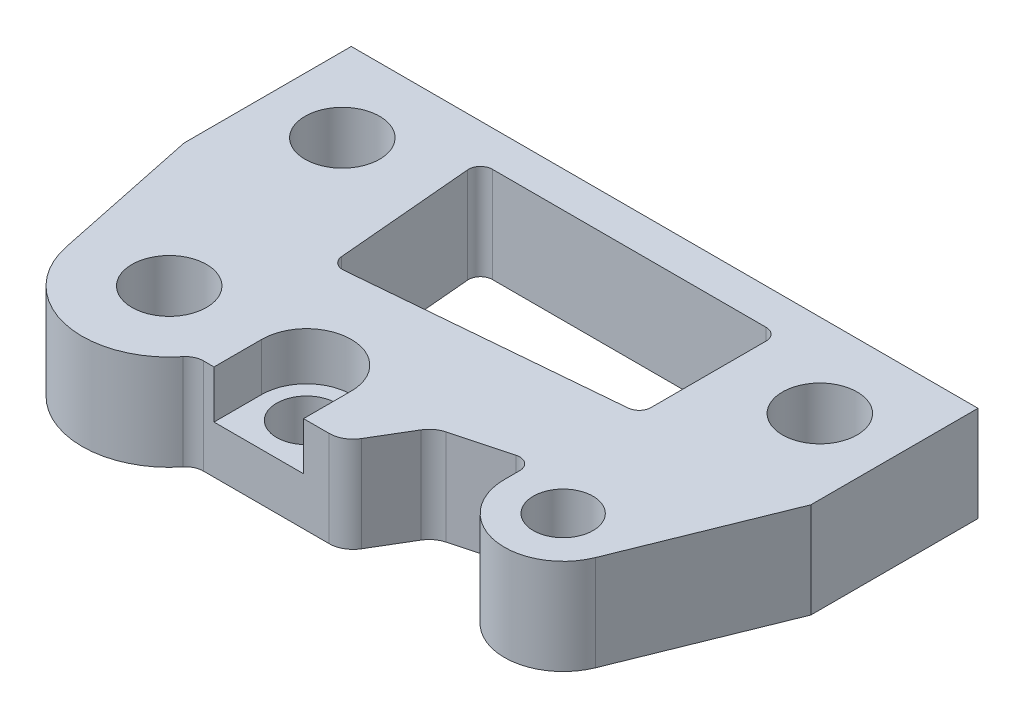
SolidWorks part; units mm, degrees
note: '?' marks a value the reader was unsure of.
material "7075-T6 (SN)"
ref_plane "X-Y Datum" through (0, 0, 0) normal (0, 0, 1) x (1, 0, 0)
ref_plane "X-Z Datum" through (0, 0, 0) normal (0, 1, 0) x (1, 0, 0)
ref_plane "Y-Z Datum" through (0, 0, 0) normal (1, 0, 0) x (0, 0, -1)
other "Graphic1"
other "Graphic (Closed) -1"
other "Graphic2"
other "Graphic (Closed) -2"
sketch "Sketch1" plane through (0, 0, 0) normal (0, 1, 0) x (1, 0, 0)
  line L0 (38.1, -5.08) -> (6.099, -5.08)
  line L1 (54.2925, 13.97) -> (-12.3825, 13.97) construction
  line L4 (54.2925, 31.75) -> (-12.3825, 31.75)
  line L6 (46.355, 22.86) -> (-4.445, 22.86) construction
  line L7 (54.2925, 31.75) -> (54.2925, 13.97)
  line L8 (-12.3825, 31.75) -> (-12.3825, 13.97)
  line L19 (48.26, 0) -> (54.2925, 13.97)
  line L21 (-7.9375, 0) -> (-12.3825, 13.97)
  line L28 (17.1395, -0.1867) -> (14.8786, 3.0422)
  line L30 (16.5708, 1.8211) -> (13.97, 0) construction
  line L31 (16.009, 1.4277) -> (11.1341, 1.4277) construction
  circle A0 centre (0, 0) radius 3.9688
  circle A1 centre (41.91, 0) radius 3.175
  circle A2 centre (46.355, 22.86) radius 3.9688
  circle A3 centre (-4.445, 22.86) radius 3.9687
  arc A4 (48.26, 0) -> (38.1, -5.08) centre (41.91, 0) cw
  arc A5 (6.099, -5.08) -> (-7.9375, 0) centre (0, 0) cw
  arc A12 (17.1395, -0.1867) -> (14.8786, 3.0422) centre (13.97, 0) cw
  point P22 (16.009, 1.4277)
  dimension "D2" = 6.35
  dimension "D7" = 7.9375
  dimension "D8" = 6.35
  dimension "D12" = 0.6858
  dimension "D10" = 7.9375
  dimension "D17" = 35
  dimension "D19" = 7.9375
  dimension "D18" = 19.05
  dimension "D14" = 3.9418
  dimension "D20" = 7.9375
  dimension "D3" = 50.8
  dimension "D4" = 17.78
  dimension "D5" = 8.89
  dimension "D6" = 31.75
  dimension "D9" = 41.91
  dimension "D11" = 7.9375
  dimension "D13" = 3.175
  dimension "D15" = 13.97
  dimension "D16" = 5.08
  dimension "D21" = 4.445
  dimension "D22" = 66.644
  dimension "D23" = 72.35
extrude "Boss-Extrude1" [suppressed] add sketch "Sketch1" against normal blind 10.16
sketch "Sketch2" [suppressed] plane through (0, 0, 0) normal (0, -1, 0) x (1, 0, 0)
  line L0 (9.2075, 0) -> (9.2075, 5.08)
  line L1 (6.099, 5.08) -> (38.1, 5.08) construction
  line L2 (9.2075, 5.08) -> (18.7325, 5.08)
  line L3 (18.7325, 5.08) -> (18.7325, 0)
  arc A0 (9.2075, 0) -> (18.7325, 0) centre (13.97, 0) ccw
  dimension "D1" = 9.525
extrude "Cut-Extrude1" [suppressed] cut sketch "Sketch2" along normal blind 5.08
ref_point "Point1" [suppressed]
ref_point "Point2" [suppressed]
ref_axis "Axis4" [suppressed] through (0, -10.16, 0) along (0, 1, 0)?
sketch "Sketch3" plane through (0, 0, 0) normal (0, 1, 0) x (1, 0, 0)
  line L0 (14.605, 0) -> (11.43, 0) construction
  line L1 (17.7745, -0.1867) -> (15.5136, 3.0422)
  line L2 (16.644, 1.4277) -> (14.605, 0) construction
  line L3 (54.2925, 31.75) -> (-12.3825, 31.75)
  line L4 (-12.3825, 31.75) -> (-12.3825, 13.97)
  line L5 (-12.3825, 13.97) -> (54.2925, 13.97) construction
  line L6 (54.2925, 13.97) -> (54.2925, 31.75)
  line L7 (54.2925, 13.97) -> (47.7027, -2.3404)
  line L10 (54.2925, 22.86) -> (46.355, 22.86) construction
  line L11 (46.355, 22.86) -> (-4.445, 22.86) construction
  line L12 (-4.445, 22.86) -> (-12.3825, 22.86) construction
  line L13 (8.7243, -5.08) -> (22.098, -5.08)
  line L16 (34.0652, 2.8527) -> (28.1745, 1.2818)
  line L17 (26.6476, 0.1288) -> (24.2794, -3.8412)
  line L18 (36.83, 14.4292) -> (36.83, 26.67)
  line L19 (35.56, 27.94) -> (6.4423, 27.94)
  line L20 (5.1772, 26.5593) -> (6.4612, 11.8834)
  line L21 (7.837, 10.7289) -> (35.6707, 13.164)
  line L22 (35.6624, 0) -> (35.6624, 1.6256)
  line L24 (-9.0759, -1.892) -> (-12.3825, 13.97)
  circle A0 centre (0, 0) radius 3.9687
  circle A1 centre (-4.445, 22.86) radius 3.9688
  circle A2 centre (46.355, 22.86) radius 3.9687
  circle A3 centre (41.91, 0) radius 3.175
  arc A4 (15.5136, 3.0422) -> (17.7745, -0.1867) centre (14.605, 0) ccw
  arc A5 (47.7027, -2.3404) -> (35.6624, 0) centre (41.91, 0) cw
  arc A6 (7.2372, -5.7944) -> (-9.0759, -1.892) centre (0, 0) cw
  arc A7 (22.098, -5.08) -> (24.2794, -3.8412) centre (22.098, -2.54) ccw
  arc A8 (26.6476, 0.1288) -> (28.1745, 1.2818) centre (28.829, -1.1724) cw
  arc A10 (6.4612, 11.8834) -> (7.837, 10.7289) centre (7.7263, 11.9941) ccw
  arc A11 (5.1772, 26.5593) -> (6.4423, 27.94) centre (6.4423, 26.67) cw
  arc A12 (35.56, 27.94) -> (36.83, 26.67) centre (35.56, 26.67) cw
  arc A13 (35.6707, 13.164) -> (36.83, 14.4292) centre (35.56, 14.4292) ccw
  arc A14 (34.0652, 2.8527) -> (35.6624, 1.6256) centre (34.3924, 1.6256) cw
  arc A16 (7.2372, -5.7944) -> (8.7243, -5.08) centre (8.7243, -6.985) cw
  point P14 (54.2925, 22.86)
  point P44 (6.5718, 10.6182)
  point P47 (5.0564, 27.94)
  point P52 (36.83, 13.2655)
  dimension "D1" = 7.9375
  dimension "D2" = 7.9375
  dimension "D3" = 6.35
  dimension "D4" = 6.35
  dimension "D14" = 9.271
  dimension "D16" = 2.54
  dimension "D23" = 1.27
  dimension "D24" = 1.27
  dimension "D28" = 4.6228
  dimension "D29" = 1.905
  dimension "D21" = 27.94
  dimension "D5" = 2.4892
  dimension "D6" = 22.86
  dimension "D7" = 145
  dimension "D8" = 7.9375
  dimension "D9" = 41.91
  dimension "D10" = 14.605
  dimension "D11" = 50.8
  dimension "D12" = 17.78
  dimension "D13" = 4.445
  dimension "D15" = 68
  dimension "D17" = 3.81
  dimension "D18" = 9.525
  dimension "D19" = 90
  dimension "D20" = 85
  dimension "D22" = 14.732
  dimension "D25" = 1.6256
  dimension "D30" = 6.985
  dimension "D31" = 22.098
  dimension "D32" = 13.081
extrude "Boss-Extrude4" add sketch "Sketch3" along normal blind 10.16
sketch "Sketch5" plane through (0, 10.16, 0) normal (0, 1, 0) x (1, 0, 0)
  line L0 (19.3675, 0) -> (19.3675, -5.08)
  line L1 (8.7243, -5.08) -> (22.098, -5.08) construction
  line L2 (19.3675, -5.08) -> (9.8425, -5.08)
  line L3 (9.8425, -5.08) -> (9.8425, 0)
  arc A0 (19.3675, 0) -> (9.8425, 0) centre (14.605, 0) ccw
  dimension "D1" = 4.7625
extrude "Cut-Extrude3" cut sketch "Sketch5" against normal blind 5.08
ref_point "Point3"
ref_point "Point4"
